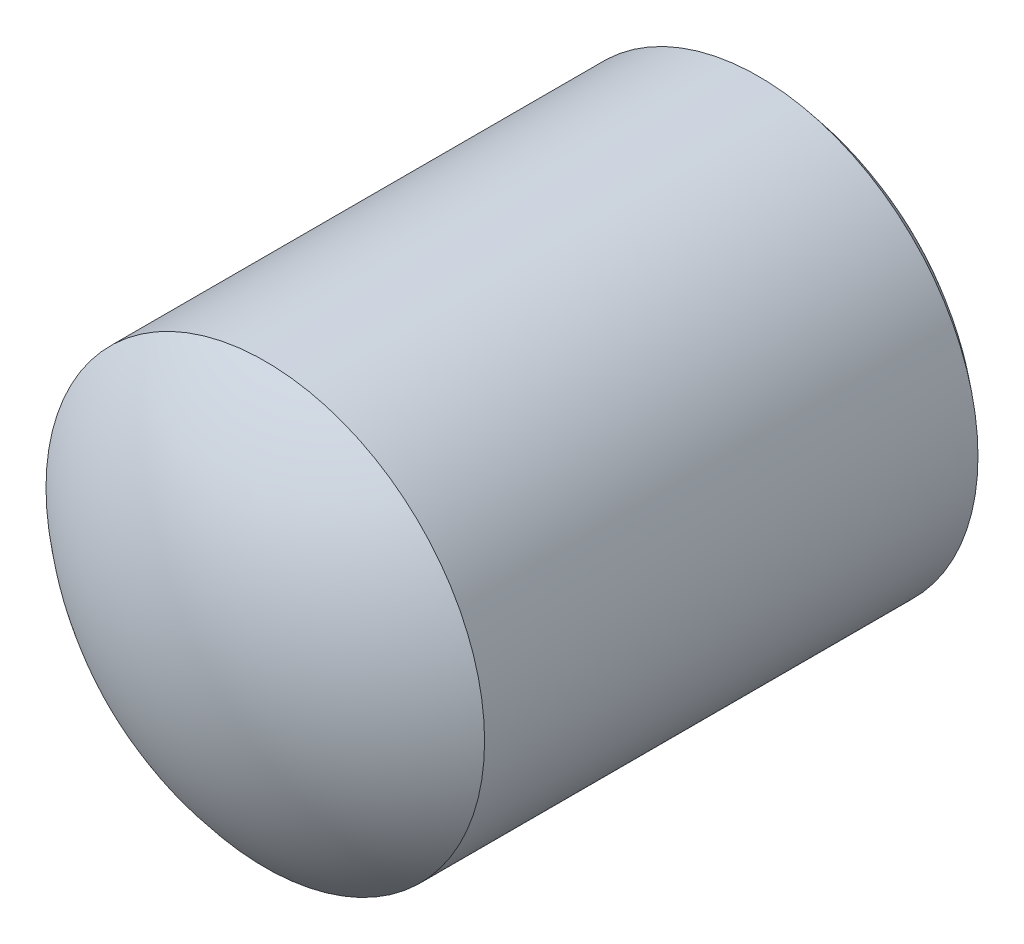
SolidWorks part; units mm, degrees
ref_plane "Front Plane" through (0, 0, 0) normal (0, 0, 1) x (1, 0, 0)
ref_plane "Top Plane" through (0, 0, 0) normal (0, 1, 0) x (1, 0, 0)
ref_plane "Right Plane" through (0, 0, 0) normal (1, 0, 0) x (0, 0, -1)
sketch "Sketch1" plane through (0, 0, 0) normal (0, 0, 1) x (1, 0, 0)
  circle A0 centre (0, 0) radius 400
  dimension "D1" = 800
extrude "Boss-Extrude1" add sketch "Sketch1" along normal blind 900
dome "Dome1" faces to dome 1 distance 150 reverse direction no elliptical dome no face at (400, 0, 900) parameters "D1"=150
dome "Dome2" faces to dome 1 distance 150 reverse direction no elliptical dome no face at (400, 0, 0) parameters "D1"=150
